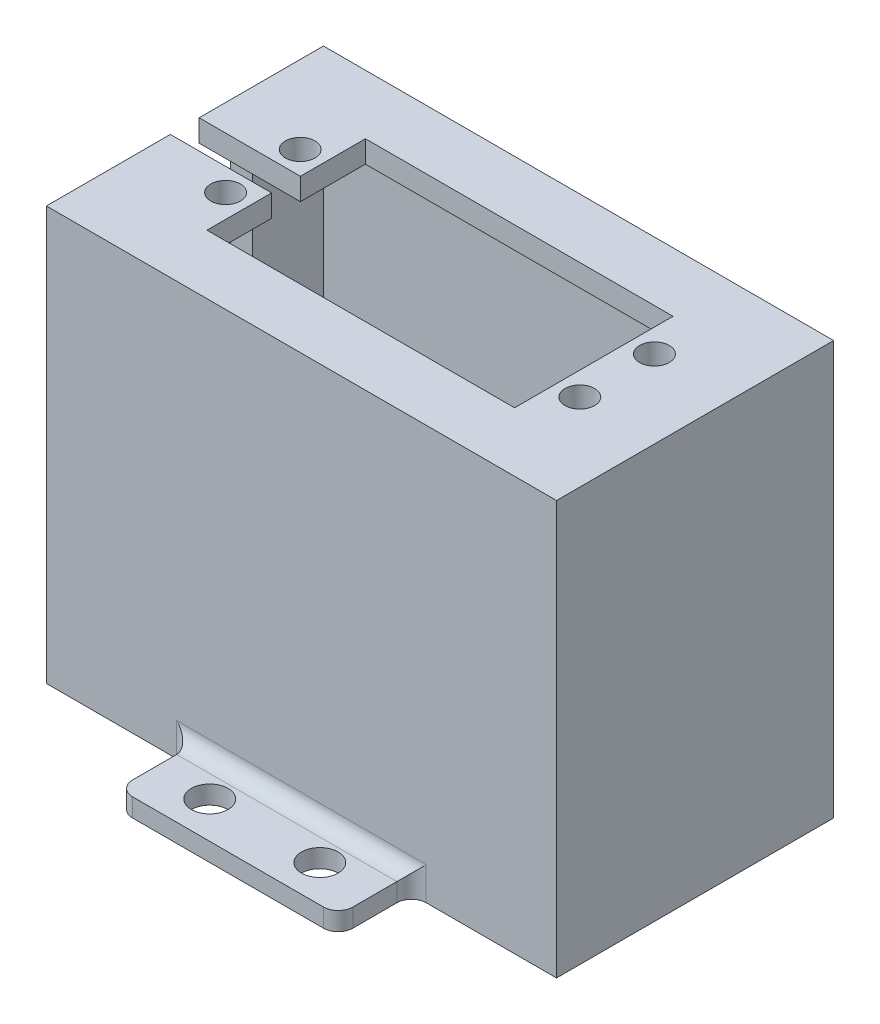
SolidWorks part; units mm, degrees
material "ABS"
ref_plane "Front Plane" through (0, 0, 0) normal (0, 0, 1) x (1, 0, 0)
ref_plane "Top Plane" through (0, 0, 0) normal (0, 1, 0) x (1, 0, 0)
ref_plane "Right Plane" through (0, 0, 0) normal (1, 0, 0) x (0, 0, -1)
sketch "Sketch1" plane through (0, 0, 0) normal (0, 1, 0) x (1, 0, 0)
  line L0 (-303.5027, 0) -> (303.5027, 0) construction
  line L1 (-223.52, -111.125) -> (223.52, -111.125)
  line L2 (-228.6, -106.045) -> (-228.6, 106.045)
  line L3 (-223.52, 111.125) -> (223.52, 111.125)
  line L4 (228.6, -106.045) -> (228.6, 106.045)
  line L5 (-228.6, -111.125) -> (228.6, 111.125) construction
  line L6 (-228.6, 111.125) -> (228.6, -111.125) construction
  line L7 (-303.5027, 36.5125) -> (303.5027, 36.5125) construction
  line L8 (-303.5027, -36.5125) -> (303.5027, -36.5125) construction
  line L9 (127, 111.125) -> (127, -111.125) construction
  line L10 (-142.24, 111.125) -> (-142.24, -111.125) construction
  arc A0 (223.52, 111.125) -> (228.6, 106.045) centre (223.52, 106.045) cw
  arc A1 (223.52, -111.125) -> (228.6, -106.045) centre (223.52, -106.045) ccw
  arc A2 (-223.52, -111.125) -> (-228.6, -106.045) centre (-223.52, -106.045) cw
  arc A3 (-228.6, 106.045) -> (-223.52, 111.125) centre (-223.52, 106.045) cw
  circle A4 centre (127, 36.5125) radius 2.54
  circle A5 centre (127, -36.5125) radius 2.54
  circle A6 centre (-142.24, 36.5125) radius 2.54
  circle A7 centre (-142.24, -36.5125) radius 2.54
  circle A8 centre (209.55, 0) radius 6.35
  point P0 (0, 0)
  point P20 (0, 0)
  point P37 (228.6, 0)
  dimension "D3" = 5.08
  dimension "D7" = 5.08
  dimension "D9" = 12.7
  dimension "D1" = 222.25
  dimension "D2" = 457.2
  dimension "D6" = 269.24
  dimension "D8" = 101.6
  dimension "D10" = 19.05
  dimension "D4" = 36.5125
  dimension "D5" = 36.5125
extrude "mainbaseplate" add sketch "Sketch1" along normal blind 3
sketch "Sketch2" plane through (0, 0, 0) normal (0, -1, 0) x (1, 0, 0)
  circle A0 centre (-142.24, 36.5125) radius 2.54 construction
  circle A1 centre (-142.24, -36.5125) radius 2.54 construction
  circle A2 centre (127, -36.5125) radius 2.54 construction
  circle A3 centre (127, 36.5125) radius 2.54 construction
  circle A4 centre (-142.24, 36.5125) radius 2.54
  circle A5 centre (-142.24, -36.5125) radius 2.54
  circle A6 centre (127, -36.5125) radius 2.54
  circle A7 centre (127, 36.5125) radius 2.54
  circle A8 centre (127, 36.5125) radius 6.096
  circle A9 centre (127, -36.5125) radius 6.096
  circle A10 centre (-142.24, -36.5125) radius 6.096
  circle A11 centre (-142.24, 36.5125) radius 6.096
  dimension "D1" = 12.192
extrude "BaseBoss-Extrude2" [suppressed] add sketch "Sketch2" along normal blind 10.16
sketch "Sketch3" plane through (0, 0, 0) normal (0, -1, 0) x (1, 0, 0)
  line L0 (-228.6, 0) -> (228.6, 0) construction
  line L1 (-228.6, -106.045) -> (-228.6, 106.045) construction
  line L2 (228.6, 106.045) -> (228.6, -106.045) construction
  line L3 (-228.6, 28.4) -> (-73.2, 28.4)
  line L4 (-228.6, -25.4) -> (-76.2, -25.4)
  line L6 (-228.6, 25.4) -> (-76.2, 25.4)
  line L7 (-76.2, -25.4) -> (-76.2, 25.4)
  line L8 (-228.6, -25.4) -> (-76.2, 25.4) construction
  line L9 (-228.6, 25.4) -> (-76.2, -25.4) construction
  line L10 (-73.2, -28.4) -> (-73.2, 28.4)
  line L11 (-228.6, -28.4) -> (-73.2, -28.4)
  line L12 (-228.6, 28.4) -> (-228.6, 25.4)
  line L13 (-228.6, -25.4) -> (-228.6, -28.4)
  point P6 (-152.4, 0)
  dimension "D1" = 50.8
  dimension "D2" = 152.4
  dimension "D3" = 76.2
  dimension "D4" = 3
extrude "Drive BatteryBoss-Extrude1" [suppressed] add sketch "Sketch3" along normal blind 28.575
sketch "Sketch4" [suppressed] plane through (0, -28.575, 0) normal (0, -1, 0) x (1, 0, 0)
  line L1 (-228.6, 28.4) -> (-73.2, 28.4)
  line L2 (-228.6, 28.4) -> (-228.6, -28.4)
  line L3 (-228.6, -28.4) -> (-73.2, -28.4)
  line L4 (-73.2, 28.4) -> (-73.2, -28.4)
extrude "drive Battery CapBoss-Extrude2" [suppressed] add sketch "Sketch4" along normal blind 3
sketch "Sketch5" [suppressed] plane through (0, -31.575, 0) normal (0, -1, 0) x (1, 0, 0)
  line L0 (-98.6, -28.4) -> (-73.2, -3)
  line L1 (-228.6, -28.4) -> (-73.2, -28.4) construction
  line L2 (-73.2, -28.4) -> (-73.2, 28.4) construction
  line L3 (-73.2, -3) -> (-52.1474, -3)
  line L4 (-52.1474, -3) -> (-52.1474, -43.6373)
  line L5 (-52.1474, -43.6373) -> (-98.6, -43.6373)
  line L6 (-98.6, -43.6373) -> (-98.6, -28.4)
  dimension "D1" = 25.4
  dimension "D2" = 25.4
  dimension "D3" = 21.0526
  dimension "D4" = 15.2373
extrude "Drive batterycutoutCut-Extrude1" [suppressed] cut sketch "Sketch5" against normal up to surface (31.575 mm away)
sketch "Sketch6" plane through (0, 3, 0) normal (0, 1, 0) x (1, 0, 0)
  line L0 (-228.6, 0) -> (228.6, 0) construction
  line L1 (-228.6, 106.045) -> (-228.6, -106.045) construction
  line L2 (228.6, -106.045) -> (228.6, 106.045) construction
  line L3 (-63.5, -41.1) -> (66.5, -41.1)
  line L4 (-63.5, -38.1) -> (63.5, -38.1)
  line L6 (-63.5, 38.1) -> (63.5, 38.1)
  line L7 (63.5, -38.1) -> (63.5, 38.1)
  line L8 (-63.5, -38.1) -> (63.5, 38.1) construction
  line L9 (-63.5, 38.1) -> (63.5, -38.1) construction
  line L10 (66.5, -41.1) -> (66.5, 41.1)
  line L11 (-63.5, 41.1) -> (66.5, 41.1)
  line L12 (-63.5, -41.1) -> (-63.5, -38.1)
  line L13 (-63.5, 38.1) -> (-63.5, 41.1)
  point P6 (0, 0)
  dimension "D1" = 127
  dimension "D2" = 76.2
  dimension "D4" = 63.5
  dimension "D3" = 3
extrude "PiBatteryBoxBoss-Extrude3" [suppressed] add sketch "Sketch6" along normal blind 25.4
sketch "Sketch7" [suppressed] plane through (0, 28.4, 0) normal (0, 1, 0) x (1, 0, 0)
  line L1 (66.5, 41.1) -> (-63.5, 41.1)
  line L2 (66.5, 41.1) -> (66.5, -41.1)
  line L3 (66.5, -41.1) -> (-63.5, -41.1)
  line L4 (-63.5, 41.1) -> (-63.5, -41.1)
extrude "PibatterytopBoss-Extrude4" [suppressed] add sketch "Sketch7" along normal blind 3
sketch "Sketch8" [suppressed] plane through (66.5, 0, 0) normal (1, 0, 0) x (0, 0, -1)
  line L0 (-38.1, 28.4) -> (38.1, 3) construction
  line L1 (38.1, 28.4) -> (-38.1, 28.4) construction
  line L2 (-31.75, 3) -> (31.75, 3)
  line L3 (-31.75, 3) -> (-31.75, 28.4)
  line L4 (-31.75, 28.4) -> (31.75, 28.4)
  line L5 (31.75, 3) -> (31.75, 28.4)
  line L6 (-31.75, 3) -> (31.75, 28.4) construction
  line L7 (-31.75, 28.4) -> (31.75, 3) construction
  point P2 (0, 15.7)
  dimension "D1" = 31.75
extrude "pibatterywiresCut-Extrude2" [suppressed] cut sketch "Sketch8" against normal blind 13.16
sketch "Sketch9" [suppressed] plane through (0, 31.4, 0) normal (0, 1, 0) x (1, 0, 0)
  line L0 (-63.5, 41.1) -> (66.5, -41.1) construction
  line L1 (-63.5, 0) -> (66.5, 0) construction
  line L2 (-5.08, -24.489) -> (52.92, -24.489) construction
  line L3 (-5.08, -24.489) -> (-5.08, 24.511) construction
  line L4 (-5.08, 24.511) -> (52.92, 24.511) construction
  line L5 (52.92, -24.489) -> (52.92, 24.511) construction
  line L6 (-5.08, -24.489) -> (52.92, 24.511) construction
  line L7 (-5.08, 24.511) -> (52.92, -24.489) construction
  line L8 (49.11, 20.701) -> (56.73, 20.701)
  line L9 (49.11, 20.701) -> (49.11, 28.321)
  line L10 (49.11, 28.321) -> (56.73, 28.321)
  line L11 (56.73, 20.701) -> (56.73, 28.321)
  line L12 (49.11, 20.701) -> (56.73, 28.321) construction
  line L13 (49.11, 28.321) -> (56.73, 20.701) construction
  line L14 (49.11, -28.299) -> (56.73, -28.299)
  line L16 (49.11, -20.679) -> (56.73, -20.679)
  line L18 (49.11, -28.299) -> (56.73, -20.679) construction
  line L19 (49.11, -20.679) -> (56.73, -28.299) construction
  line L20 (-8.89, 20.701) -> (-1.27, 20.701)
  line L21 (-8.89, 20.701) -> (-8.89, 28.321)
  line L22 (-8.89, 28.321) -> (-1.27, 28.321)
  line L23 (-1.27, 20.701) -> (-1.27, 28.321)
  line L24 (-8.89, 20.701) -> (-1.27, 28.321) construction
  line L25 (-8.89, 28.321) -> (-1.27, 20.701) construction
  line L26 (-8.89, -27.7078) -> (-1.27, -27.7078)
  line L27 (-8.89, -27.7078) -> (-8.89, -21.2702)
  line L28 (-8.89, -21.2702) -> (-1.27, -21.2702)
  line L29 (-1.27, -27.7078) -> (-1.27, -21.2702)
  line L30 (-8.89, -27.7078) -> (-1.27, -21.2702) construction
  line L31 (-8.89, -21.2702) -> (-1.27, -27.7078) construction
  line L32 (-63.5, 41.1) -> (-63.5, -41.1) construction
  line L33 (66.5, -41.1) -> (66.5, 41.1) construction
  line L34 (56.73, -20.679) -> (56.73, -28.299)
  line L35 (49.11, -20.679) -> (49.11, -28.299)
  circle A0 centre (52.92, 24.511) radius 1.35
  circle A1 centre (-5.08, 24.511) radius 1.35
  circle A2 centre (-5.08, -24.489) radius 1.35
  circle A3 centre (52.92, -24.489) radius 1.35
  point P4 (-8.057, 0)
  dimension "D3" = 2.7
  dimension "D4" = 7.62
  dimension "D1" = 58
  dimension "D2" = 49
  dimension "D5" = 7.62
  dimension "D6" = 7.62
  dimension "D7" = 7.62
  dimension "D8" = 7.62
  dimension "D9" = 7.62
  dimension "D10" = 58.42
  dimension "D11" = 24.511
  dimension "D12" = 7.62
extrude "PiBoardBoss-Extrude5" [suppressed] add sketch "Sketch9" along normal blind 3
sketch "Sketch10" plane through (0, 3, 0) normal (0, 1, 0) x (1, 0, 0)
  line L0 (228.6, 0) -> (-228.6, 0) construction
  line L1 (228.6, -106.045) -> (228.6, 106.045) construction
  line L2 (-228.6, 106.045) -> (-228.6, -106.045) construction
  line L3 (104.95, 18.875) -> (174.45, 18.875)
  line L4 (107.95, -15.875) -> (171.45, -15.875)
  line L5 (107.95, -15.875) -> (107.95, -6.175)
  line L6 (107.95, 15.875) -> (171.45, 15.875)
  line L7 (171.45, -15.875) -> (171.45, 15.875)
  line L8 (107.95, -15.875) -> (171.45, 15.875) construction
  line L9 (107.95, 15.875) -> (171.45, -15.875) construction
  line L10 (174.45, -18.875) -> (174.45, 18.875)
  line L11 (104.95, -18.875) -> (174.45, -18.875)
  line L12 (104.95, -18.875) -> (104.95, -6.175)
  line L13 (104.95, 6.175) -> (107.95, 6.175)
  line L14 (104.95, -6.175) -> (107.95, -6.175)
  line L15 (104.95, 6.175) -> (104.95, 18.875)
  line L16 (104.95, -18.875) -> (104.95, 18.875) construction
  line L17 (107.95, 6.175) -> (107.95, 15.875)
  line L18 (107.95, -15.875) -> (107.95, 15.875) construction
  point P6 (139.7, 0)
  dimension "D1" = 31.75
  dimension "D2" = 63.5
  dimension "D3" = 139.7
  dimension "D5" = 12.7
  dimension "D6" = 12.7
  dimension "D4" = 3
extrude "PanTilt-Extrude6" add sketch "Sketch10" along normal blind 53.34
sketch "Sketch11" plane through (0, 56.34, 0) normal (0, 1, 0) x (1, 0, 0)
  line L1 (104.95, 18.875) -> (174.45, 18.875)
  line L2 (104.95, 18.875) -> (104.95, -18.875)
  line L3 (104.95, -18.875) -> (174.45, -18.875)
  line L4 (174.45, 18.875) -> (174.45, -18.875)
extrude "Boss-Extrude7" add sketch "Sketch11" along normal blind 3
sketch "Sketch12" plane through (0, 59.34, 0) normal (0, 1, 0) x (1, 0, 0)
  line L0 (104.95, 0) -> (174.45, 0) construction
  line L1 (104.95, 18.875) -> (104.95, -18.875) construction
  line L2 (174.45, -18.875) -> (174.45, 18.875) construction
  line L3 (118.745, 1.9377) -> (104.95, 1.9377)
  line L4 (118.745, -10.795) -> (160.655, -10.795)
  line L5 (118.745, -10.795) -> (118.745, -1.9901)
  line L6 (118.745, 10.795) -> (160.655, 10.795)
  line L7 (160.655, -10.795) -> (160.655, 10.795)
  line L8 (118.745, -10.795) -> (160.655, 10.795) construction
  line L9 (118.745, 10.795) -> (160.655, -10.795) construction
  line L10 (115.57, -5.08) -> (163.83, -5.08) construction
  line L11 (115.57, -5.08) -> (115.57, 5.08) construction
  line L12 (115.57, 5.08) -> (163.83, 5.08) construction
  line L13 (163.83, -5.08) -> (163.83, 5.08) construction
  line L14 (115.57, -5.08) -> (163.83, 5.08) construction
  line L15 (115.57, 5.08) -> (163.83, -5.08) construction
  line L16 (118.745, -1.9901) -> (104.95, -1.9901)
  line L17 (118.745, 1.9377) -> (118.745, 10.795)
  line L18 (104.95, 1.9377) -> (95.8416, 0)
  line L19 (95.8416, 0) -> (104.95, -1.9901)
  circle A0 centre (163.83, 5.08) radius 2.0193
  circle A1 centre (163.83, -5.08) radius 2.0193
  circle A2 centre (115.57, 5.08) radius 2.0193
  circle A3 centre (115.57, -5.08) radius 2.0193
  point P6 (139.7, 0)
  point P11 (139.7, 0)
  dimension "D5" = 4.0386
  dimension "D1" = 21.59
  dimension "D2" = 41.91
  dimension "D3" = 48.26
  dimension "D4" = 10.16
  dimension "D6" = 1.9377
  dimension "D7" = 1.9901
extrude "Cut-Extrude3" cut sketch "Sketch12" against normal up to surface (56.34 mm away) up to face at (209.55, 3, 6.35)
sketch "Sketch13" plane through (0, 3, 0) normal (0, 1, 0) x (1, 0, 0)
  line L0 (228.6, 0) -> (-228.6, 0) construction
  line L1 (228.6, -106.045) -> (228.6, 106.045) construction
  line L2 (-228.6, 106.045) -> (-228.6, -106.045) construction
  line L3 (198.12, 0) -> (198.12, 25.4)
  line L4 (198.12, 25.4) -> (172.72, 69.3941)
  line L5 (172.72, 69.3941) -> (136.799, 105.3151)
  line L6 (198.12, 25.4) -> (198.12, 129.9736) construction
  line L7 (172.72, 69.3941) -> (172.72, 97.5573) construction
  line L8 (136.799, 105.3151) -> (-185.781, 105.3151)
  line L9 (-185.781, 105.3151) -> (-221.702, 69.3941)
  line L10 (-221.702, 69.3941) -> (-221.702, 0)
  line L11 (-185.781, 105.3151) -> (-290.6809, 105.3151) construction
  line L12 (195.12, 0) -> (195.12, 24.5962)
  line L13 (195.12, 24.5962) -> (170.3194, 67.552)
  line L14 (170.3194, 67.552) -> (135.5563, 102.3151)
  line L15 (135.5563, 102.3151) -> (-184.5384, 102.3151)
  line L16 (-184.5384, 102.3151) -> (-218.702, 68.1514)
  line L17 (-218.702, 68.1514) -> (-218.702, 0)
  line L18 (172.72, -69.3941) -> (172.72, -97.5573) construction
  line L19 (198.12, -25.4) -> (198.12, -129.9736) construction
  line L20 (-218.702, -68.1514) -> (-218.702, 0)
  line L21 (-184.5384, -102.3151) -> (-218.702, -68.1514)
  line L22 (135.5563, -102.3151) -> (-184.5384, -102.3151)
  line L23 (170.3194, -67.552) -> (135.5563, -102.3151)
  line L24 (195.12, -24.5962) -> (170.3194, -67.552)
  line L25 (195.12, 0) -> (195.12, -24.5962)
  line L26 (-221.702, -69.3941) -> (-221.702, 0)
  line L27 (-185.781, -105.3151) -> (-221.702, -69.3941)
  line L28 (136.799, -105.3151) -> (-185.781, -105.3151)
  line L29 (172.72, -69.3941) -> (136.799, -105.3151)
  line L30 (198.12, -25.4) -> (172.72, -69.3941)
  line L31 (198.12, 0) -> (198.12, -25.4)
  dimension "D1" = 30.48
  dimension "D2" = 25.4
  dimension "D3" = 30
  dimension "D4" = 50.8
  dimension "D5" = 45
  dimension "D6" = 50.8
  dimension "D7" = 322.58
  dimension "D8" = 50.8
  dimension "D9" = 45
  dimension "D10" = 3
extrude "Bottom Shell WallsBoss-Extrude8" [suppressed] add sketch "Sketch13" along normal blind 68.58
sketch "Sketch14" [suppressed] plane through (121.057, 0, -121.057) normal (0.7071, 0, -0.7071) x (-0.7071, 0, -0.7071)
  line L0 (-47.6625, 71.58) -> (-47.6625, 3) construction
  line L1 (-73.0625, 71.58) -> (-22.2625, 71.58) construction
  line L2 (-73.0625, 3) -> (-22.2625, 3) construction
  line L3 (-47.6625, 37.29) -> (-25.0131, 37.29) construction
  circle A0 centre (-47.6625, 64.722) radius 1.3526
  circle A1 centre (-47.6625, 9.858) radius 1.3526
  circle A2 centre (-29.8825, 37.29) radius 4.7625
  point P10 (-47.6625, 37.29)
  dimension "D1" = 2.7051
  dimension "D4" = 9.525
  dimension "D2" = 54.864
  dimension "D3" = 27.432
  dimension "D5" = 17.78
extrude "Sharp1Cut-Extrude4" [suppressed] cut sketch "Sketch14" against normal blind 12.7
sketch "Sketch15" [suppressed] plane through (159.5885, 0, -92.1385) normal (0.866, 0, -0.5) x (-0.5, 0, -0.866)
  line L0 (-51.663, 71.58) -> (-51.663, 3) construction
  line L1 (-77.063, 71.58) -> (-26.263, 71.58) construction
  line L2 (-77.063, 3) -> (-26.263, 3) construction
  line L3 (-51.663, 37.29) -> (-29.7061, 37.29) construction
  circle A0 centre (-51.663, 64.722) radius 1.3526
  circle A1 centre (-51.663, 9.858) radius 1.3526
  circle A2 centre (-33.883, 37.29) radius 4.7625
  point P10 (-51.663, 37.29)
  dimension "D1" = 2.7051
  dimension "D4" = 9.525
  dimension "D2" = 27.432
  dimension "D3" = 54.864
  dimension "D5" = 17.78
extrude "Sharp2Cut-Extrude5" [suppressed] cut sketch "Sketch15" against normal blind 7.62
sketch "Sketch16" [suppressed] plane through (198.12, 0, 0) normal (1, 0, 0) x (0, 0, -1)
  line L0 (0, 71.58) -> (0, 3) construction
  line L1 (-25.4, 71.58) -> (25.4, 71.58) construction
  line L2 (-25.4, 3) -> (25.4, 3) construction
  line L3 (0, 37.29) -> (21.2381, 37.29) construction
  circle A0 centre (0, 64.722) radius 1.3526
  circle A1 centre (0, 9.858) radius 1.3525
  circle A2 centre (17.78, 37.29) radius 4.7625
  dimension "D1" = 2.7051
  dimension "D4" = 9.525
  dimension "D2" = 27.432
  dimension "D3" = 54.864
  dimension "D5" = 17.78
extrude "Sharp3Cut-Extrude6" [suppressed] cut sketch "Sketch16" against normal blind 7.62
sketch "Sketch17" [suppressed] plane through (159.5885, 0, 92.1385) normal (0.866, 0, 0.5) x (0.5, 0, -0.866)
  line L0 (51.663, 71.58) -> (51.663, 3) construction
  line L1 (26.263, 71.58) -> (77.063, 71.58) construction
  line L2 (26.263, 3) -> (77.063, 3) construction
  line L3 (51.663, 37.29) -> (70.4023, 37.29) construction
  circle A0 centre (51.663, 64.722) radius 1.3526
  circle A1 centre (51.663, 9.858) radius 1.3526
  circle A2 centre (69.443, 37.29) radius 4.7625
  dimension "D1" = 2.7051
  dimension "D2" = 2.7051
  dimension "D3" = 9.525
  dimension "D4" = 17.78
  dimension "D5" = 27.432
  dimension "D6" = 54.864
extrude "SharpCut-Extrude7" [suppressed] cut sketch "Sketch17" against normal blind 7.62
sketch "Sketch18" [suppressed] plane through (121.057, 0, 121.057) normal (0.7071, 0, 0.7071) x (0.7071, 0, -0.7071)
  line L0 (47.6625, 71.58) -> (47.6625, 3) construction
  line L1 (22.2625, 71.58) -> (73.0625, 71.58) construction
  line L2 (22.2625, 3) -> (73.0625, 3) construction
  line L3 (25.604, 37.29) -> (69.7209, 37.29) construction
  circle A0 centre (47.6625, 64.722) radius 1.3526
  circle A1 centre (47.6625, 9.858) radius 1.3526
  circle A2 centre (65.4425, 37.29) radius 4.7625
  point P13 (47.6625, 37.29)
  dimension "D1" = 9.525
  dimension "D3" = 2.7051
  dimension "D4" = 2.7051
  dimension "D2" = 17.78
  dimension "D5" = 27.432
  dimension "D6" = 54.864
extrude "SharpCut-Extrude8" [suppressed] cut sketch "Sketch18" against normal blind 7.62
sketch "Sketch19" [suppressed] plane through (0, 71.58, 0) normal (0, 1, 0) x (1, 0, 0)
  line L0 (-223.52, -111.125) -> (223.52, -111.125) construction
  line L1 (228.6, -106.045) -> (228.6, 106.045) construction
  line L2 (223.52, 111.125) -> (-223.52, 111.125) construction
  line L3 (104.95, -111.125) -> (223.52, -111.125)
  line L4 (228.6, -106.045) -> (228.6, 106.045)
  line L5 (223.52, 111.125) -> (104.95, 111.125)
  line L6 (104.95, 111.125) -> (104.95, -111.125)
  arc A0 (223.52, -111.125) -> (228.6, -106.045) centre (223.52, -106.045) ccw construction
  arc A1 (228.6, 106.045) -> (223.52, 111.125) centre (223.52, 106.045) ccw construction
  arc A2 (223.52, -111.125) -> (228.6, -106.045) centre (223.52, -106.045) ccw
  arc A3 (228.6, 106.045) -> (223.52, 111.125) centre (223.52, 106.045) ccw
extrude "TopSensorplateBoss-Extrude8" [suppressed] add sketch "Sketch19" along normal blind 3
sketch "Sketch21" [suppressed] plane through (0, 74.58, 0) normal (0, 1, 0) x (1, 0, 0)
  line L0 (104.95, -18.875) -> (174.45, -18.875) construction
  line L1 (174.45, -18.875) -> (174.45, 18.875) construction
  line L2 (174.45, 18.875) -> (104.95, 18.875) construction
  line L3 (104.95, -18.875) -> (164.29, -18.875)
  line L4 (174.45, -8.715) -> (174.45, 8.715)
  line L5 (164.29, 18.875) -> (104.95, 18.875)
  line L6 (104.95, 18.875) -> (84.8462, 2.2825)
  line L7 (84.8462, 2.2825) -> (104.95, -18.875)
  arc A0 (164.29, -18.875) -> (174.45, -8.715) centre (164.29, -8.715) ccw
  arc A1 (174.45, 8.715) -> (164.29, 18.875) centre (164.29, 8.715) ccw
  circle A2 centre (127, -36.5125) radius 6.096 construction
  circle A3 centre (127, 36.5125) radius 6.096 construction
  circle A4 centre (127, -36.5125) radius 6.096
  circle A5 centre (127, 36.5125) radius 6.096
  dimension "D1" = 10.16
extrude "topsensorplateCut-Extrude4" [suppressed] cut sketch "Sketch21" against normal blind 8.08
sketch "Sketch22" [suppressed] plane through (0, 0, 0) normal (0, -1, 0) x (1, 0, 0)
  line L0 (228.6, 0) -> (-228.6, 0) construction
  line L1 (228.6, 106.045) -> (228.6, -106.045) construction
  line L2 (-228.6, 28.4) -> (-228.6, -28.4) construction
  line L3 (220.98, 0) -> (220.98, 76.2)
  line L4 (220.98, 76.2) -> (193.675, 103.505)
  line L5 (193.675, 103.505) -> (-25.4, 103.505)
  line L6 (-223.52, 111.125) -> (223.52, 111.125) construction
  line L7 (217.98, 0) -> (217.98, 74.9574)
  line L8 (217.98, 74.9574) -> (192.4324, 100.505)
  line L9 (192.4324, 100.505) -> (-25.4, 100.505)
  line L10 (-25.4, 103.505) -> (-25.4, 100.505)
  line L11 (217.98, 0) -> (217.98, -74.9574)
  line L12 (220.98, 0) -> (220.98, -76.2)
  line L13 (-25.4, -103.505) -> (-25.4, -100.505)
  line L14 (192.4324, -100.505) -> (-25.4, -100.505)
  line L15 (217.98, -74.9574) -> (192.4324, -100.505)
  line L16 (193.675, -103.505) -> (-25.4, -103.505)
  line L17 (220.98, -76.2) -> (193.675, -103.505)
  line L18 (-220.98, 28.4) -> (-220.98, 76.2)
  line L19 (-73.2, 28.4) -> (-228.6, 28.4) construction
  line L20 (-220.98, 76.2) -> (-193.548, 103.505)
  line L21 (-193.548, 103.505) -> (-127, 103.505)
  line L22 (-228.6, 28.4) -> (-228.6, 106.045) construction
  line L23 (-217.98, 28.4) -> (-217.98, 74.9533)
  line L24 (-217.98, 74.9533) -> (-192.3094, 100.505)
  line L25 (-192.3094, 100.505) -> (-127, 100.505)
  line L26 (-127, 103.505) -> (-127, 100.505)
  line L27 (-220.98, 28.4) -> (-217.98, 28.4)
  line L28 (-127, -103.505) -> (-127, -100.505)
  line L29 (-192.3094, -100.505) -> (-127, -100.505)
  line L30 (-217.98, -74.9533) -> (-192.3094, -100.505)
  line L31 (-217.98, -28.4) -> (-217.98, -74.9533)
  line L32 (-193.548, -103.505) -> (-127, -103.505)
  line L33 (-220.98, -76.2) -> (-193.548, -103.505)
  line L34 (-220.98, -28.4) -> (-220.98, -76.2)
  line L35 (-220.98, -28.4) -> (-217.98, -28.4)
  dimension "D1" = 7.62
  dimension "D2" = 7.62
  dimension "D3" = 76.2
  dimension "D4" = 34.925
  dimension "D5" = 254
  dimension "D7" = 7.62
  dimension "D8" = 76.2
  dimension "D9" = 7.62
  dimension "D10" = 101.6
  dimension "D11" = 35.052
  dimension "D6" = 3
  dimension "D12" = 3
extrude "frontrockerpanBoss-Extrude9" [suppressed] add sketch "Sketch22" along normal blind 45.72
sketch "Sketch23" [suppressed] plane through (0, 0, -103.505) normal (0, 0, -1) x (-1, 0, 0)
  line L0 (25.4, 0) -> (-193.675, 0) construction
  line L2 (-223.1134, -81.0052) -> (22.7571, -81.0052) construction
  line L3 (22.7571, -81.0052) -> (254.0819, -81.0052) construction
  circle A1 centre (-127, -81.0052) radius 63.5
  circle A2 centre (152.4, -81.0052) radius 63.5
  dimension "D1" = 81.0052
  dimension "D4" = 127
  dimension "D2" = 22.7571
  dimension "D3" = 223.1134
  dimension "D5" = 127
  dimension "D6" = 279.4
extrude "TireCut-Extrude5" [suppressed] cut sketch "Sketch23" against normal blind 25.4
sketch "Sketch24" [suppressed] plane through (-221.702, 0, 0) normal (-1, 0, 0) x (0, 0, 1)
  line L0 (-69.3941, 71.58) -> (69.3941, 3) construction
  circle A0 centre (0, 37.29) radius 10.9855
  dimension "D1" = 21.971
extrude "Cut-Extrude6" [suppressed] cut sketch "Sketch24" against normal blind 7.62
sketch "Sketch25" [suppressed] plane through (0, 71.58, 0) normal (0, 1, 0) x (1, 0, 0)
  line L3 (-223.52, -111.125) -> (223.52, -111.125) construction
  line L5 (-228.6, 106.045) -> (-228.6, -106.045) construction
  line L6 (223.52, 111.125) -> (-223.52, 111.125) construction
  line L7 (-223.52, -111.125) -> (-147.32, -111.125)
  line L8 (-228.6, 106.045) -> (-228.6, -106.045)
  line L9 (-147.32, 111.125) -> (-223.52, 111.125)
  line L10 (-147.32, 111.125) -> (-147.32, -111.125)
  arc A2 (-228.6, -106.045) -> (-223.52, -111.125) centre (-223.52, -106.045) ccw construction
  arc A3 (-223.52, 111.125) -> (-228.6, 106.045) centre (-223.52, 106.045) ccw construction
  arc A4 (-228.6, -106.045) -> (-223.52, -111.125) centre (-223.52, -106.045) ccw
  arc A5 (-223.52, 111.125) -> (-228.6, 106.045) centre (-223.52, 106.045) ccw
  dimension "D1" = 147.32
extrude "ReartopdeckBoss-Extrude10" [suppressed] add sketch "Sketch25" along normal blind 3
sketch "Sketch28" [suppressed] plane through (0, 0, 103.505) normal (0, 0, 1) x (1, 0, 0)
  line L0 (-205.194, -45.72) -> (-93.1399, -108.4782)
  line L1 (-93.1399, -108.4782) -> (179.794, -45.72)
  line L2 (74.206, -45.72) -> (-102.0458, -69.7467)
  line L3 (-102.0458, -69.7467) -> (-127, -22.8065)
  arc A0 (-192.3094, -31.6141) -> (-205.194, -45.72) centre (-152.4, -81.0052) ccw construction
  arc A1 (-127, -22.8065) -> (-192.3094, -31.6141) centre (-152.4, -81.0052) ccw construction
  arc A2 (179.794, -45.72) -> (74.206, -45.72) centre (127, -81.0052) ccw construction
  arc A3 (-192.3094, -31.6141) -> (-205.194, -45.72) centre (-152.4, -81.0052) ccw
  arc A4 (-127, -22.8065) -> (-192.3094, -31.6141) centre (-152.4, -81.0052) ccw
  arc A5 (179.794, -45.72) -> (74.206, -45.72) centre (127, -81.0052) ccw
extrude "TireCut-Extrude8" [suppressed] cut sketch "Sketch28" against normal blind 35.56
sketch "Sketch30" [suppressed] plane through (0, 74.58, 0) normal (0, 1, 0) x (1, 0, 0)
  line L0 (-147.32, 0) -> (-228.6, 0) construction
  line L1 (-147.32, -111.125) -> (-147.32, 111.125) construction
  line L2 (-228.6, 106.045) -> (-228.6, -106.045) construction
  circle A0 centre (-166.37, 0) radius 6.35
  dimension "D1" = 12.7
  dimension "D2" = 19.05
extrude "Cut-Extrude10" [suppressed] cut sketch "Sketch30" against normal blind 11.684
sketch "Sketch31" [suppressed] plane through (0, 0, 0) normal (1, 0, 0) x (0, 0, -1)
  line L0 (102.3151, 71.58) -> (102.3151, 3) construction
  line L1 (-102.3151, 71.58) -> (-76.9151, 71.58)
  line L2 (-102.3151, 71.58) -> (-102.3151, 68.58)
  line L3 (-102.3151, 68.58) -> (-76.9151, 68.58)
  line L4 (102.3151, 71.58) -> (102.3151, 68.58)
  line L5 (-76.9151, 71.58) -> (-76.9151, 68.58)
  line L6 (76.9151, 71.58) -> (76.9151, 68.58)
  line L7 (76.9151, 71.58) -> (102.3151, 71.58)
  line L8 (76.9151, 68.58) -> (102.3151, 68.58)
  dimension "D1" = 3
  dimension "D2" = 25.4
  dimension "D3" = 25.4
extrude "Boss-Extrude8" [suppressed] add sketch "Sketch31" along normal blind 134.62 and the other way blind 180.34
sketch "Sketch32" plane through (0, 0, 0) normal (0, -1, 0) x (1, 0, 0)
  line L1 (-362.1056, 298.8668) -> (350.2899, 298.8668)
  line L2 (-362.1056, 298.8668) -> (-362.1056, -225.3293)
  line L3 (-362.1056, -225.3293) -> (350.2899, -225.3293)
  line L4 (350.2899, 298.8668) -> (350.2899, -225.3293)
extrude "Cut-Extrude11" cut sketch "Sketch32" against normal up to surface (3 mm away) up to face at (209.55, 3, 6.35)
sketch "Sketch33" plane through (0, 3, 0) normal (0, -1, 0) x (1, 0, 0)
  line L0 (174.45, 0) -> (90.833, 0) construction
  line L1 (154.7, 28.875) -> (124.7, 28.875)
  line L2 (154.7, 28.875) -> (154.7, -28.875)
  line L3 (154.7, -28.875) -> (124.7, -28.875)
  line L4 (124.7, 28.875) -> (124.7, -28.875)
  line L5 (174.45, 18.875) -> (174.45, -18.875) construction
  line L6 (104.95, 18.875) -> (174.45, 18.875) construction
  line L7 (174.45, -18.875) -> (104.95, -18.875) construction
  line L8 (139.7, -18.875) -> (139.7, 50.2921) construction
  line L9 (147.2, 28.875) -> (147.2, 18.875) construction
  line L10 (154.7, -18.875) -> (124.7, -18.875)
  line L11 (154.7, 18.875) -> (124.7, 18.875)
  circle A0 centre (147.2, 23.875) radius 2.5
  circle A1 centre (132.2, 23.875) radius 2.5
  circle A2 centre (132.2, -23.875) radius 2.5
  circle A3 centre (147.2, -23.875) radius 2.5
  point P9 (139.7, 28.875)
  point P14 (139.7, -28.875)
  point P16 (154.7, 0)
  point P22 (147.2, 23.875)
  line M13 (104.95, -18.875) -> (174.45, -18.875)
  line M15 (174.45, 18.875) -> (104.95, 18.875)
  dimension "D3" = 5
  dimension "D4" = 7.5
  dimension "D1" = 10
  dimension "D2" = 30
extrude "Boss-Extrude9" add sketch "Sketch33" against normal blind 2.5 contours L1 L4 L2 A0 A1 M15 | L4 L3 L2 A2 A3 M13 region at (139.7, 3, 23.875) region at (139.7, 3, -23.875)
fillet "Fillet1" radius 2 10 edges at (154.7, 4.25, 28.875) (124.7, 4.25, 28.875) (124.7, 4.25, 18.875) (154.7, 4.25, 18.875) (139.7, 5.5, 18.875) (124.7, 4.25, -28.875) (124.7, 4.25, -18.875) (154.7, 4.25, -28.875) (154.7, 4.25, -18.875) (139.7, 5.5, -18.875)
